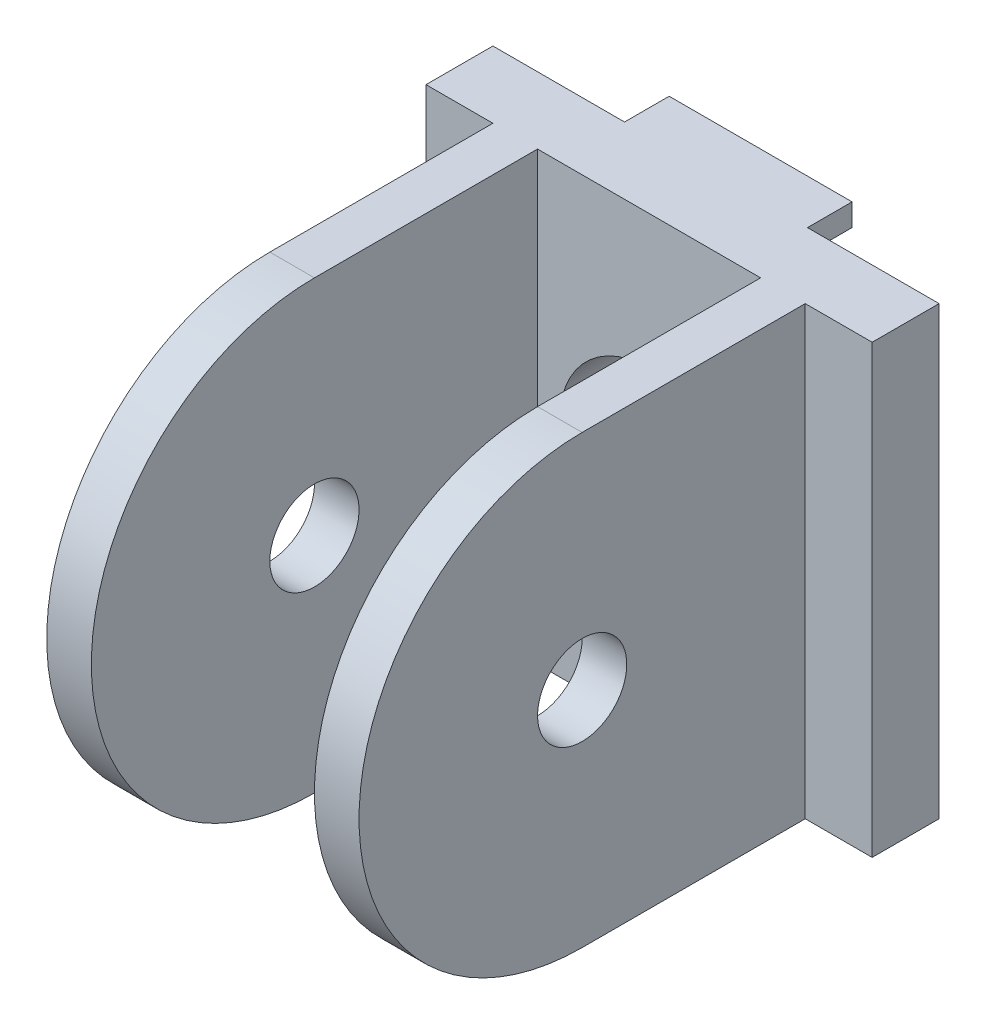
SolidWorks part; units mm, degrees
ref_plane "前视基准面" through (0, 0, 0) normal (0, 0, 1) x (1, 0, 0)
ref_plane "上视基准面" through (0, 0, 0) normal (0, 1, 0) x (1, 0, 0)
ref_plane "右视基准面" through (0, 0, 0) normal (1, 0, 0) x (0, 0, -1)
sketch "草图1" plane through (0, 0, 0) normal (0, 0, 1) x (1, 0, 0)
  line L1 (-10, -10) -> (10, -10)
  line L2 (-10, -10) -> (-10, 10)
  line L3 (-10, 10) -> (10, 10)
  line L4 (10, -10) -> (10, 10)
  line L5 (-10, -10) -> (10, 10) construction
  line L6 (-10, 10) -> (10, -10) construction
  point P0 (0, 0)
  dimension "D1" = 20
  dimension "D2" = 20
extrude "凸台-拉伸1" add sketch "草图1" along normal blind 3
sketch "草图2" plane through (0, 0, 3) normal (0, 0, 1) x (1, 0, 0)
  line L0 (10, 10) -> (-10, 10) construction
  line L1 (-7, -10) -> (-5, -10)
  line L2 (-7, -10) -> (-7, 10)
  line L3 (-7, 10) -> (-5, 10)
  line L4 (-5, -10) -> (-5, 10)
  line L5 (-7, -10) -> (-5, 10) construction
  line L6 (-7, 10) -> (-5, -10) construction
  line L7 (-10, 10) -> (-10, -10) construction
  line L8 (0, 0) -> (0, 12.1648) construction
  line L9 (7, -10) -> (5, -10)
  line L10 (7, -10) -> (7, 10)
  line L11 (5, -10) -> (5, 10)
  line L12 (7, 10) -> (5, 10)
  line L13 (-10, -10) -> (10, -10) construction
  point P0 (-6, 0)
  dimension "D1" = 2
  dimension "D2" = 3
extrude "凸台-拉伸2" add sketch "草图2" along normal blind 20
sketch "草图3" plane through (-7, 0, 0) normal (-1, 0, 0) x (0, 0, 1)
  line L0 (23, 10) -> (23, -10) construction
  line L1 (23, 10) -> (3, 10) construction
  line L2 (23, -10) -> (3, -10) construction
  arc A0 (13, -10) -> (13, 10) centre (13, 0) ccw
  dimension "D1" = 20
extrude "切除-拉伸2" cut sketch "草图3" against normal through all and the other way through all flip side to cut
sketch "草图4" plane through (-7, 0, 0) normal (-1, 0, 0) x (0, 0, 1)
  circle A0 centre (13, 0) radius 2
  dimension "D1" = 4
extrude "切除-拉伸3" cut sketch "草图4" against normal through all
sketch "草图6" plane through (0, 0, 3) normal (0, 0, 1) x (1, 0, 0)
  circle A0 centre (0, 0) radius 4
  dimension "D1" = 8
extrude "切除-拉伸5" cut sketch "草图6" against normal through all
sketch "草图7" plane through (0, 0, 0) normal (0, 0, -1) x (-1, 0, 0)
  line L0 (0, 0) -> (-17.0155, 0) construction
  line L1 (-10, 10) -> (10, 10) construction
  line L2 (-4.1, 10) -> (4.1, 10)
  line L3 (-4.1, 10) -> (-4.1, 9)
  line L4 (-4.1, 9) -> (4.1, 9)
  line L5 (4.1, 10) -> (4.1, 9)
  line L6 (4.1, -10) -> (4.1, -9)
  line L7 (-4.1, -10) -> (-4.1, -9)
  line L8 (-4.1, -9) -> (4.1, -9)
  line L9 (-4.1, -10) -> (4.1, -10)
  point P9 (0, 10)
  point P10 (0, 10)
  dimension "D1" = 1
  dimension "D2" = 8.2
extrude "凸台-拉伸3" add sketch "草图7" along normal blind 2
